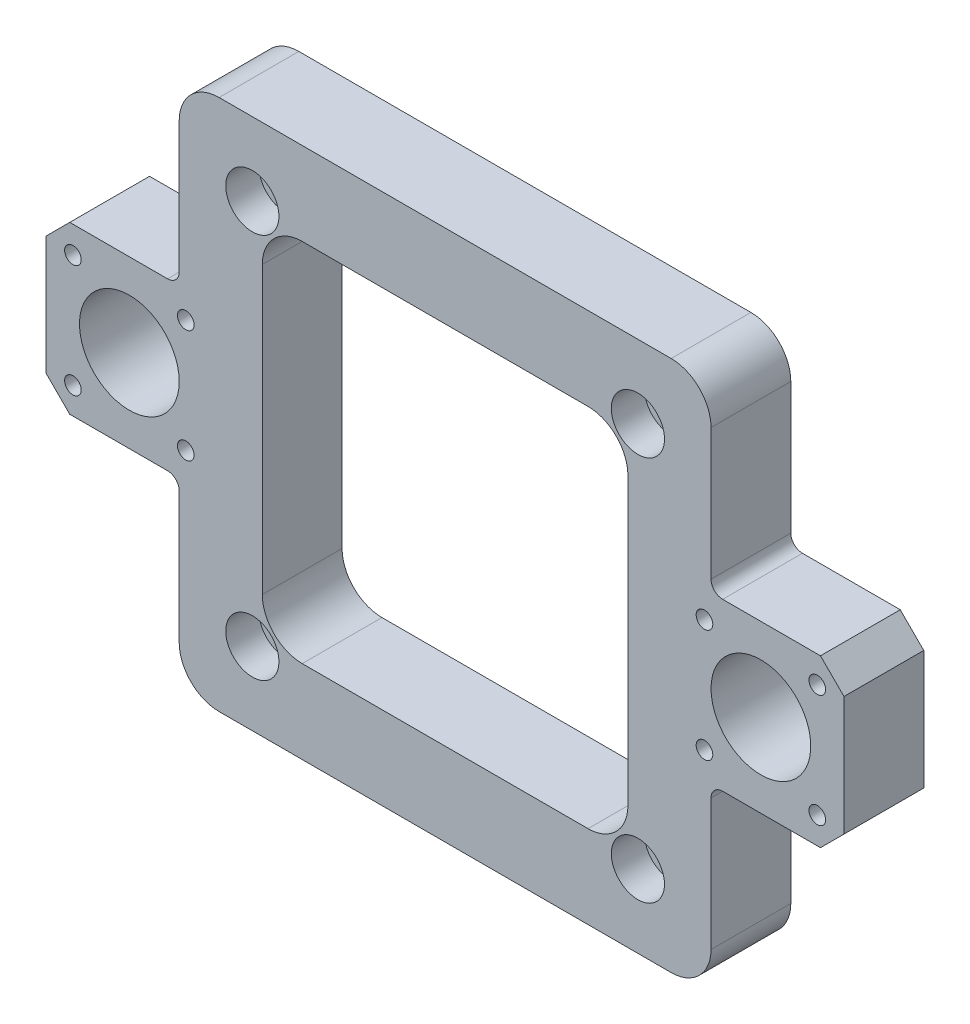
SolidWorks part; units mm, degrees
ref_plane "Front Plane" through (0, 0, 0) normal (0, 0, 1) x (1, 0, 0)
ref_plane "Top Plane" through (0, 0, 0) normal (0, 1, 0) x (1, 0, 0)
ref_plane "Right Plane" through (0, 0, 0) normal (1, 0, 0) x (0, 0, -1)
sketch "Sketch1" plane through (0, 0, 0) normal (0, 0, 1) x (1, 0, 0)
  line L0 (-47.5, 0) -> (47.5, 0) construction
  line L1 (0, 0) -> (0, 17.3262) construction
  line L2 (-56.4645, 12.5) -> (-41.75, 12.5)
  line L3 (-40, 14.25) -> (-40, 34)
  line L12 (-56.4645, 12.5) -> (-60, 8.9645)
  line L13 (-60, 8.9645) -> (-60, -8.9645)
  line L14 (34, 40) -> (-34, 40)
  line L15 (60, 8.9645) -> (60, -8.9645)
  line L16 (56.4645, 12.5) -> (60, 8.9645)
  line L17 (56.4645, 12.5) -> (41.75, 12.5)
  line L18 (40, 14.25) -> (40, 34)
  line L19 (-56.4645, -12.5) -> (-60, -8.9645)
  line L20 (-56.4645, -12.5) -> (-41.75, -12.5)
  line L21 (-40, -14.25) -> (-40, -34)
  line L22 (34, -40) -> (-34, -40)
  line L23 (40, -14.25) -> (40, -34)
  line L24 (56.4645, -12.5) -> (41.75, -12.5)
  line L25 (56.4645, -12.5) -> (60, -8.9645)
  line L26 (-55.9853, 8.4853) -> (-39.0147, -8.4853) construction
  line L27 (-55.9853, -8.4853) -> (-39.0147, 8.4853) construction
  circle A0 centre (-47.5, 0) radius 7.5
  arc A12 (-41.75, 12.5) -> (-40, 14.25) centre (-41.75, 14.25) ccw
  arc A13 (-40, 34) -> (-34, 40) centre (-34, 34) cw
  arc A14 (41.75, 12.5) -> (40, 14.25) centre (41.75, 14.25) cw
  arc A15 (40, 34) -> (34, 40) centre (34, 34) ccw
  arc A16 (-41.75, -12.5) -> (-40, -14.25) centre (-41.75, -14.25) cw
  arc A17 (-40, -34) -> (-34, -40) centre (-34, -34) ccw
  arc A18 (40, -34) -> (34, -40) centre (34, -34) cw
  arc A19 (41.75, -12.5) -> (40, -14.25) centre (41.75, -14.25) ccw
  circle A20 centre (47.5, 0) radius 7.5
  circle A21 centre (-55.9853, 8.4853) radius 1.75 construction
  circle A22 centre (-39.0147, -8.4853) radius 1.75 construction
  circle A23 centre (-39.0147, 8.4853) radius 1.75 construction
  circle A24 centre (-55.9853, -8.4853) radius 1.75 construction
  circle A25 centre (39.0147, -8.4853) radius 1.75 construction
  circle A26 centre (55.9853, -8.4853) radius 1.75 construction
  circle A27 centre (55.9853, 8.4853) radius 1.75 construction
  circle A28 centre (39.0147, 8.4853) radius 1.75 construction
  circle A29 centre (-29, 29) radius 2.75 construction
  circle A33 centre (29, 29) radius 2.75 construction
  circle A34 centre (29, -29) radius 2.75 construction
  circle A35 centre (-29, -29) radius 2.75 construction
  point P28 (0, 40)
  point P29 (-60, 0)
  point P44 (60, 0)
  dimension "D2" = 15
  dimension "D3" = 25
  dimension "D6" = 1.75
  dimension "D11" = 3.5
  dimension "D13" = 6
  dimension "D15" = 5.5
  dimension "D1" = 95
  dimension "D4" = 120
  dimension "D5" = 40
  dimension "D7" = 135
  dimension "D8" = 80
  dimension "D9" = 5
  dimension "D10" = 24
  dimension "D12" = 135
  dimension "D14" = 58
  dimension "D16" = 58
extrude "Boss-Extrude1" add sketch "Sketch1" along normal blind 12
sketch "m4basefasteners" plane through (0, 0, 0) normal (0, 0, -1) x (-1, 0, 0)
  circle A0 centre (-29, -29) radius 2.75 construction
  circle A1 centre (-29, 29) radius 2.75 construction
  circle A2 centre (29, 29) radius 2.75 construction
  circle A3 centre (29, -29) radius 2.75 construction
  point P0 (-29, 29)
  point P1 (29, 29)
  point P2 (29, -29)
  point P3 (-29, -29)
  point P4 (-54.2426, -31.3801)
  point P7 (-76.3925, 40.2996)
  point P10 (25.2402, 41.9945)
  point P13 (23.4859, -27.3185)
sketch "Sketch4" [suppressed] plane through (0, 0, 12) normal (0, 0, 1) x (1, 0, 0)
  circle A0 centre (55.9853, 8.4853) radius 1.75 construction
  circle A1 centre (55.9853, -8.4853) radius 1.75 construction
  circle A2 centre (39.0147, -8.4853) radius 1.75 construction
  circle A3 centre (39.0147, 8.4853) radius 1.75 construction
  circle A4 centre (-39.0147, 8.4853) radius 1.75 construction
  circle A5 centre (-39.0147, -8.4853) radius 1.75 construction
  circle A6 centre (-55.9853, -8.4853) radius 1.75 construction
  circle A7 centre (-55.9853, 8.4853) radius 1.75 construction
  circle A8 centre (55.9853, 8.4853) radius 1.75
  circle A9 centre (55.9853, -8.4853) radius 1.75
  circle A10 centre (39.0147, -8.4853) radius 1.75
  circle A11 centre (39.0147, 8.4853) radius 1.75
  circle A12 centre (-39.0147, 8.4853) radius 1.75
  circle A13 centre (-39.0147, -8.4853) radius 1.75
  circle A14 centre (-55.9853, -8.4853) radius 1.75
  circle A15 centre (-55.9853, 8.4853) radius 1.75
extrude "Cut-Extrude3" [suppressed] cut sketch "Sketch4" against normal through all both and the other way through all
sketch "Sketch2" plane through (0, 0, 12) normal (0, 0, 1) x (1, 0, 0)
  line L0 (-21.5, 21.5) -> (21.5, -21.5) construction
  line L1 (-21.5, 27.5) -> (21.5, 27.5)
  line L2 (-27.5, 21.5) -> (-27.5, -21.5)
  line L3 (-21.5, -27.5) -> (21.5, -27.5)
  line L4 (27.5, 21.5) -> (27.5, -21.5)
  arc A0 (-27.5, -21.5) -> (-21.5, -27.5) centre (-21.5, -21.5) ccw
  arc A1 (21.5, -27.5) -> (27.5, -21.5) centre (21.5, -21.5) ccw
  arc A2 (27.5, 21.5) -> (21.5, 27.5) centre (21.5, 21.5) ccw
  arc A3 (-21.5, 27.5) -> (-27.5, 21.5) centre (-21.5, 21.5) ccw
  dimension "D1" = 6
  dimension "D2" = 55
extrude "Cut-Extrude1" cut sketch "Sketch2" against normal through all both and the other way through all
sketch "Sketch3" plane through (0, 0, 12) normal (0, 0, 1) x (1, 0, 0)
  line L0 (-56.4645, 12.5) -> (-60, 8.9645) construction
  line L1 (-55.1485, 5.3623) -> (-52.8623, 7.6485)
  line L2 (-52.8623, 7.6485) -> (-53.6991, 10.7715)
  line L3 (-53.6991, 10.7715) -> (-56.8221, 11.6083)
  line L4 (-56.8221, 11.6083) -> (-59.1083, 9.3221)
  line L5 (-59.1083, 9.3221) -> (-58.2715, 6.1991)
  line L6 (-58.2715, 6.1991) -> (-55.1485, 5.3623)
  line L7 (-42.1377, 7.6485) -> (-39.8515, 5.3623)
  line L8 (-39.8515, 5.3623) -> (-36.7285, 6.1991)
  line L9 (-36.7285, 6.1991) -> (-35.8917, 9.3221)
  line L10 (-35.8917, 9.3221) -> (-38.1779, 11.6083)
  line L11 (-38.1779, 11.6083) -> (-41.3009, 10.7715)
  line L12 (-41.3009, 10.7715) -> (-42.1377, 7.6485)
  line L13 (-39.8515, -5.3623) -> (-42.1377, -7.6485)
  line L14 (-42.1377, -7.6485) -> (-41.3009, -10.7715)
  line L15 (-41.3009, -10.7715) -> (-38.1779, -11.6083)
  line L16 (-38.1779, -11.6083) -> (-35.8917, -9.3221)
  line L17 (-35.8917, -9.3221) -> (-36.7285, -6.1991)
  line L18 (-36.7285, -6.1991) -> (-39.8515, -5.3623)
  line L19 (-52.8623, -7.6485) -> (-55.1485, -5.3623)
  line L20 (-55.1485, -5.3623) -> (-58.2715, -6.1991)
  line L21 (-58.2715, -6.1991) -> (-59.1083, -9.3221)
  line L22 (-59.1083, -9.3221) -> (-56.8221, -11.6083)
  line L23 (-56.8221, -11.6083) -> (-53.6991, -10.7715)
  line L24 (-53.6991, -10.7715) -> (-52.8623, -7.6485)
  circle A0 centre (-55.9853, 8.4853) radius 2.8 construction
  circle A2 centre (-47.5, 0) radius 7.5 construction
  circle A3 centre (-47.5, 0) radius 7.5 construction
  circle A4 centre (-39.0147, 8.4853) radius 2.8 construction
  circle A5 centre (-39.0147, -8.4853) radius 2.8 construction
  circle A6 centre (-55.9853, -8.4853) radius 2.8 construction
  point P42 (-47.5, 0)
  dimension "D1" = 5.6
  dimension "D2" = 4
extrude "Cut-Extrude2" [suppressed] cut sketch "Sketch3" against normal blind 2.5
mirror "Mirror1" [suppressed] about plane through (0, 0, 0) normal (1, 0, 0)
sketch "Sketch5" plane through (0, 0, 0) normal (0, 0, -1) x (-1, 0, 0)
  point P0 (55.9853, -8.4853)
  point P3 (55.9853, 8.4853)
  point P6 (39.0147, 8.4853)
  point P9 (39.0147, -8.4853)
  point P12 (-39.0147, -8.4853)
  point P15 (-39.0147, 8.4853)
  point P18 (-55.9853, 8.4853)
  point P21 (-55.9853, -8.4853)
hole_wizard "Tap Drill for M3x0.5 Tap1" positions "Sketch5" profile "Sketch6" hole size "M3x0.5" standard "ANSI Metric" end condition through all
sketch "Sketch6" plane through (-55.9853, -8.4853, 0) normal (1, 0, 0) x (0, 1, 0)
  line L0 (0, 0) -> (0, 12)
  line L1 (0, 12) -> (1.25, 12)
  line L2 (1.25, 12) -> (1.25, 0)
  line L5 (1.25, 0) -> (0, 0)
  line L11 (0, -6.35) -> (0, 107.95) construction
  dimension "Thru Hole Dia." = 2.5
  dimension "Thru Hole Depth" = 12
sketch "Sketch7" [suppressed] plane through (0, 0, 0) normal (0, 0, -1) x (-1, 0, 0)
  circle A0 centre (29, -29) radius 1.75
  circle A1 centre (29, -29) radius 2.75 construction
  circle A2 centre (-29, 29) radius 1.75
  circle A3 centre (-29, -29) radius 1.75
  circle A4 centre (29, 29) radius 1.75
  circle A5 centre (-29, -29) radius 2.75 construction
  circle A6 centre (29, 29) radius 2.75 construction
  circle A7 centre (-29, 29) radius 2.75 construction
  dimension "D1" = 3.5
extrude "Cut-Extrude4" [suppressed] cut sketch "Sketch7" against normal through all
sketch "Sketch8" [suppressed] plane through (0, 0, 12) normal (0, 0, 1) x (1, 0, 0)
  line L1 (-27.3834, 26.2) -> (-25.7668, 29)
  line L2 (-25.7668, 29) -> (-27.3834, 31.8)
  line L3 (-27.3834, 31.8) -> (-30.6166, 31.8)
  line L4 (-30.6166, 31.8) -> (-32.2332, 29)
  line L5 (-32.2332, 29) -> (-30.6166, 26.2)
  line L6 (-30.6166, 26.2) -> (-27.3834, 26.2)
  line L7 (-27.3834, -31.8) -> (-25.7668, -29)
  line L8 (-25.7668, -29) -> (-27.3834, -26.2)
  line L9 (-27.3834, -26.2) -> (-30.6166, -26.2)
  line L10 (-30.6166, -26.2) -> (-32.2332, -29)
  line L11 (-32.2332, -29) -> (-30.6166, -31.8)
  line L12 (-30.6166, -31.8) -> (-27.3834, -31.8)
  line L13 (30.6166, -31.8) -> (32.2332, -29)
  line L14 (32.2332, -29) -> (30.6166, -26.2)
  line L15 (30.6166, -26.2) -> (27.3834, -26.2)
  line L16 (27.3834, -26.2) -> (25.7668, -29)
  line L17 (25.7668, -29) -> (27.3834, -31.8)
  line L18 (27.3834, -31.8) -> (30.6166, -31.8)
  line L19 (30.6166, 26.2) -> (32.2332, 29)
  line L20 (32.2332, 29) -> (30.6166, 31.8)
  line L21 (30.6166, 31.8) -> (27.3834, 31.8)
  line L22 (27.3834, 31.8) -> (25.7668, 29)
  line L23 (25.7668, 29) -> (27.3834, 26.2)
  line L24 (27.3834, 26.2) -> (30.6166, 26.2)
  circle A0 centre (-29, 29) radius 2.8 construction
  circle A1 centre (-29, -29) radius 2.8 construction
  circle A2 centre (29, -29) radius 2.8 construction
  circle A3 centre (29, 29) radius 2.8 construction
  dimension "D1" = 5.6
extrude "Cut-Extrude5" [suppressed] cut sketch "Sketch8" against normal blind 2.5
sketch "Sketch9" plane through (0, 0, 12) normal (0, 0, -1) x (-1, 0, 0)
  point P0 (29, -29)
  point P3 (29, 29)
  point P6 (-29, 29)
  point P9 (-29, -29)
hole_wizard "CBORE for M4 Hex Socket Head Cap Screw1" positions "Sketch9" profile "Sketch10" counterbore size "M4" standard "DIN" end condition through all
sketch "Sketch10" plane through (-29, -29, 12) normal (1, 0, 0) x (0, -1, 0)
  line L0 (0, 0) -> (0, 12)
  line L1 (0, 12) -> (2.15, 12)
  line L3 (2.15, 12) -> (2.15, 5)
  line L4 (2.15, 5) -> (4, 5)
  line L5 (4, 5) -> (4, 0)
  line L7 (4, 0) -> (0, 0)
  line L11 (0, -6.35) -> (0, 107.95) construction
  dimension "Thru Hole Dia." = 4.3
  dimension "Thru Hole Depth" = 12
  dimension "C'Bore Dia." = 8
  dimension "C'Bore Depth" = 5
